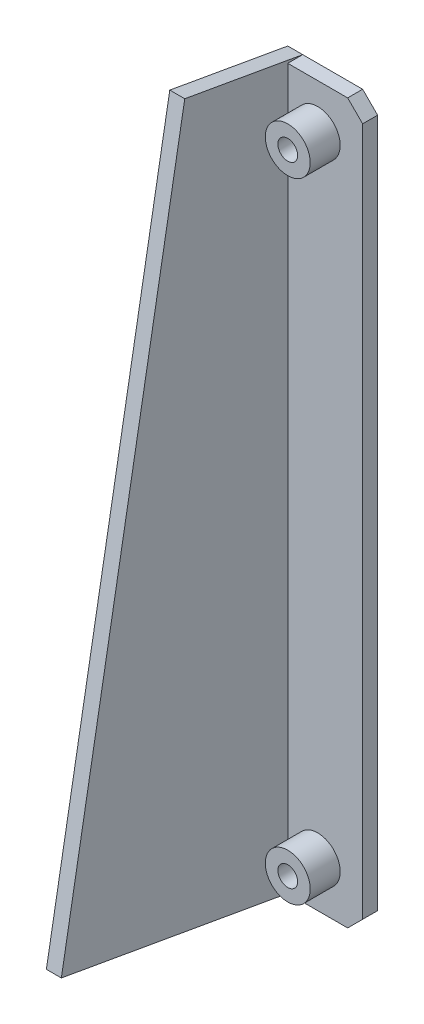
SolidWorks part; units mm, degrees
ref_plane "Front Plane" through (0, 0, 0) normal (0, 0, 1) x (1, 0, 0)
ref_plane "Top Plane" through (0, 0, 0) normal (0, 1, 0) x (1, 0, 0)
ref_plane "Right Plane" through (0, 0, 0) normal (1, 0, 0) x (0, 0, -1)
sketch "Sketch1" plane through (0, 0, 0) normal (0, 0, 1) x (1, 0, 0)
  line L1 (0, 0) -> (-9.525, 0)
  line L2 (0, 0) -> (0, 76.2)
  line L3 (0, 76.2) -> (-9.525, 76.2)
  line L4 (-9.525, 0) -> (-9.525, 76.2)
  dimension "D1" = 76.2
  dimension "D2" = 9.525
extrude "Boss-Extrude1" add sketch "Sketch1" along normal blind 1.5875
chamfer "Chamfer2" distance 1.5875 angle 45 4 edges at (0, 76.2, 0.7937) (-9.525, 76.2, 0.7937) (0, 0, 0.7937) (-9.525, 0, 0.7937)
hole_wizard "#97 (0.0825) Diameter Hole1" positions "Sketch2" profile "Sketch3" hole size "#97" standard "ANSI Inch" end condition through all
sketch "Sketch2" plane through (0, 0, 1.5875) normal (0, 0, 1) x (1, 0, 0)
  line L0 (-1.5875, 76.2) -> (-7.9375, 76.2) construction
  line L1 (-7.9375, 0) -> (-1.5875, 0) construction
  line L2 (0, 4.7625) -> (-9.525, 4.7625) construction
  line L3 (0, 1.5875) -> (0, 74.6125) construction
  line L4 (-9.525, 74.6125) -> (-9.525, 1.5875) construction
  point P0 (-4.7625, 4.7625)
  point P2 (-4.7625, 71.4375)
  dimension "D1" = 4.7625
  dimension "D2" = 4.7625
sketch "Sketch3" plane through (-4.7625, 4.7625, 1.5875) normal (1, 0, 0) x (0, -1, 0)
  line L0 (0, 0) -> (0, 1.5875)
  line L1 (0, 1.5875) -> (1.0477, 1.5875)
  line L2 (1.0477, 1.5875) -> (1.0477, 0)
  line L5 (1.0477, 0) -> (0, 0)
  line L11 (0, -6.35) -> (0, 107.95) construction
  dimension "Thru Hole Dia." = 2.0955
  dimension "Thru Hole Depth" = 1.5875
ref_plane "Plane1" through (0, 38.1, 0) normal (0, 1, 0) x (1, 0, 0)
sketch "Sketch5" plane through (0, 0, 1.5875) normal (0, 0, 1) x (1, 0, 0)
  line L0 (0.8731, 38.1) -> (-0.8731, 38.1) construction
  circle A0 centre (-4.7625, 4.7625) radius 1.0478
  circle A1 centre (-4.7625, 4.7625) radius 2.3813
  circle A2 centre (-4.7625, 71.4375) radius 2.3813
  circle A3 centre (-4.7625, 71.4375) radius 1.0477
  dimension "D1" = 4.7625
  dimension "D2" = 2.0955
extrude "Boss-Extrude2" add sketch "Sketch5" along normal blind 3.175
sketch "Sketch6" plane through (0, 0, 1.5875) normal (0, 0, 1) x (1, 0, 0)
  line L1 (-9.525, 74.6125) -> (-7.9375, 74.6125)
  line L2 (-9.525, 74.6125) -> (-9.525, 1.5875)
  line L3 (-9.525, 1.5875) -> (-7.9375, 1.5875)
  line L4 (-7.9375, 74.6125) -> (-7.9375, 1.5875)
  dimension "D1" = 1.5875
ref_plane "Plane2" through (0, 2.2977, 13.031) normal (0, -0.1736, -0.9848) x (-1, 0, 0)
sketch "Sketch7" plane through (0, 2.2977, 13.031) normal (0, -0.1736, -0.9848) x (-1, 0, 0)
  line L1 (9.525, 75.0424) -> (7.9375, 75.0424)
  line L2 (9.525, 75.0424) -> (9.525, -0.2757)
  line L3 (9.525, -0.2757) -> (7.9375, -0.2757)
  line L4 (7.9375, 75.0424) -> (7.9375, -0.2757)
  line L8 (1.5875, 75.0424) -> (7.9375, 75.0424) construction
  line L9 (9.525, 73.479) -> (9.525, 1.5634) construction
  line L10 (7.9375, -0.2757) -> (1.5875, -0.2757) construction
extrude "Boss-Extrude4" add sketch "Sketch7" along normal up to surface and the other way blind 12.7 up to face at (-2.3813, 4.7625, 1.5875)
sketch "Sketch8" plane through (0, 2.2977, 13.031) normal (0, -0.1736, -0.9848) x (-1, 0, 0)
  line L0 (9.525, 74.9937) -> (9.525, 75.0424)
  line L1 (9.525, 73.4304) -> (9.525, 75.0424) construction
  line L2 (9.525, 75.0424) -> (7.9375, 75.0424)
  line L3 (7.9375, 75.0424) -> (9.525, 74.9937)
extrude "Boss-Extrude5" add sketch "Sketch8" along normal up to surface up to face at (-3.7148, 4.7625, 0)
